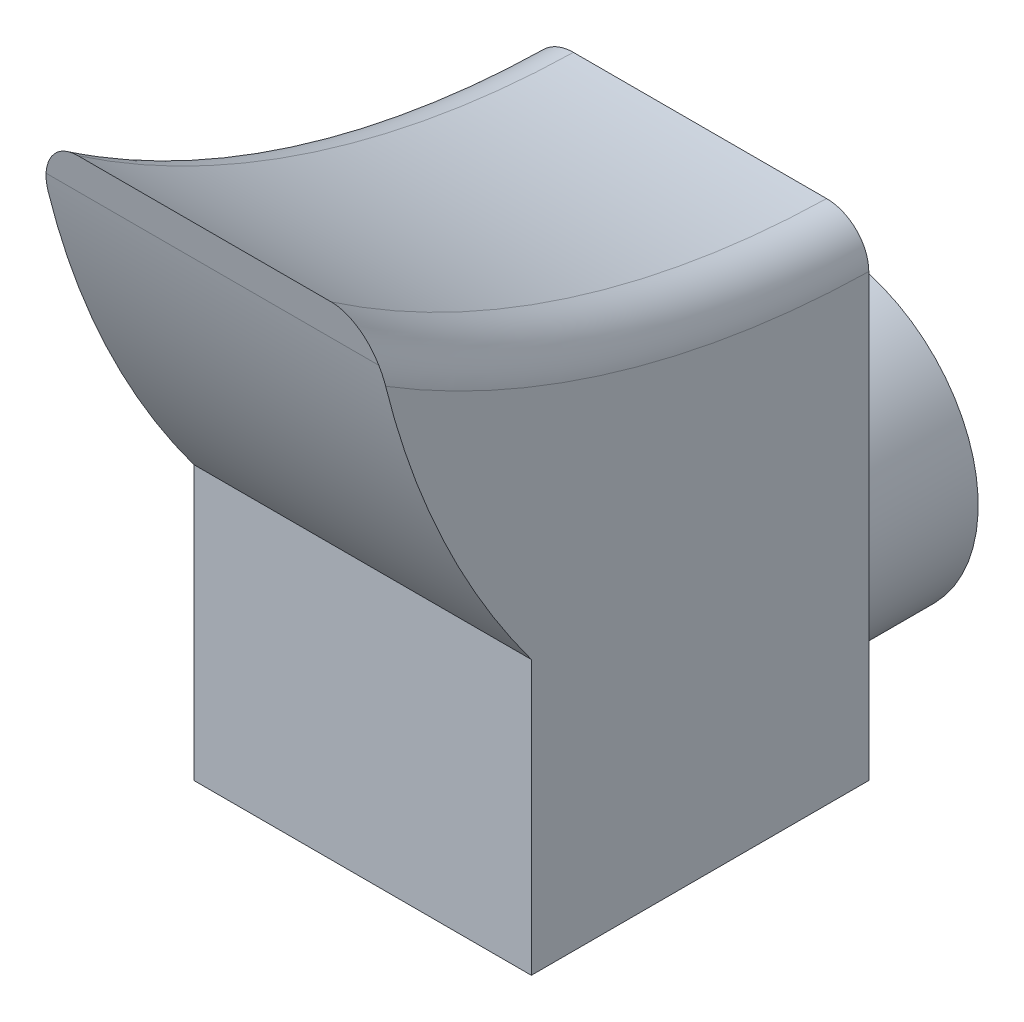
SolidWorks part; units mm, degrees
ref_plane "Front Plane" through (0, 0, 0) normal (0, 0, 1) x (1, 0, 0)
ref_plane "Top Plane" through (0, 0, 0) normal (0, 1, 0) x (1, 0, 0)
ref_plane "Right Plane" through (0, 0, 0) normal (1, 0, 0) x (0, 0, -1)
sketch "Sketch1" plane through (0, 0, 0) normal (0, 0, 1) x (1, 0, 0)
  line L6 (-39.1338, -35.8463) -> (-39.1338, -33.2005)
  line L7 (-42.1338, -35.8462) -> (-42.1338, -33.2005)
  line L10 (-40.6338, -38.5234) -> (-38.6289, -38.5234)
  line L11 (-40.6338, -38.5234) -> (-42.6335, -38.4759)
  line L13 (-42.4445, -30.5234) -> (-40.6338, -30.5234)
  line L14 (-38.6289, -38.5234) -> (-38.6289, -30.5234)
  line L15 (-38.6289, -30.5234) -> (-40.6338, -30.5234)
  line L16 (-42.6335, -38.4759) -> (-42.6335, -30.5234)
  line L17 (-42.6335, -30.5234) -> (-42.4445, -30.5234)
  arc A6 (-42.1338, -35.8462) -> (-39.1338, -35.8463) centre (-40.6338, -34.5234) ccw
  arc A7 (-39.1338, -33.2005) -> (-42.1338, -33.2005) centre (-40.6338, -34.5234) ccw
extrude "Boss-Extrude1" add sketch "Sketch1" against normal blind 5
sketch "Sketch2" plane through (-38.6289, 0, 0) normal (1, 0, 0) x (0, 0, -1)
  line L4 (0, -30.5234) -> (0, -38.5234)
  line L5 (0, -38.5234) -> (5, -38.5234)
  line L6 (5, -38.5234) -> (5, -30.5234)
  line L7 (5, -30.5234) -> (0, -30.5234)
  line L8 (0, -30.5234) -> (0, -38.5234)
  line L9 (0, -38.5234) -> (5, -38.5234)
  line L10 (5, -38.5234) -> (5, -30.5234)
  line L11 (5, -30.5234) -> (0, -30.5234)
  dimension "D1" = 0
extrude "Boss-Extrude2" add sketch "Sketch2" along normal blind 1
sketch "Sketch3" plane through (-42.6335, 0, 0) normal (-1, 0, 0) x (0, 0, 1)
  line L4 (0, -38.4759) -> (0, -30.5234)
  line L5 (0, -30.5234) -> (-5, -30.5234)
  line L6 (-5, -30.5234) -> (-5, -38.4759)
  line L7 (-5, -38.4759) -> (0, -38.4759)
  line L8 (0, -38.4759) -> (0, -30.5234)
  line L9 (0, -30.5234) -> (-5, -30.5234)
  line L10 (-5, -30.5234) -> (-5, -38.4759)
  line L11 (-5, -38.4759) -> (0, -38.4759)
  dimension "D1" = 0
extrude "Boss-Extrude3" add sketch "Sketch3" along normal blind 1
sketch "Sketch4" plane through (0, 0, 0) normal (0, 0, 1) x (1, 0, 0)
  circle A0 centre (-40.6338, -34.5232) radius 2.6168
  arc A2 (-38.6219, -36.1966) -> (-38.0838, -35.1107) centre (-40.6337, -34.5233) ccw
  arc A3 (-38.0838, -33.936) -> (-38.6219, -32.8502) centre (-40.6337, -34.5234) ccw
  arc A4 (-42.6457, -32.8502) -> (-43.1838, -33.936) centre (-40.6338, -34.5234) ccw
  arc A5 (-43.1838, -35.1107) -> (-42.6457, -36.1966) centre (-40.6338, -34.5233) ccw
  spline S6 degree 3 poles (-38.6836, -36.2325) (-38.6587, -36.2324) (-38.6377, -36.2156) (-38.6219, -36.1966) knots 0 0 0 0 0.000073 0.000073 0.000073 0.000073 weights 1 1 1 1
  spline S7 degree 3 poles (-38.6219, -32.8502) (-38.6376, -32.8312) (-38.6586, -32.8145) (-38.6834, -32.8142) knots 0 0 0 0 0.000073 0.000073 0.000073 0.000073 weights 1 1 1 1
  spline S12 degree 3 poles (-42.6457, -36.1966) (-42.6298, -36.2155) (-42.6086, -36.2322) (-42.5838, -36.2321) knots 0 0 0 0 0.000073 0.000073 0.000073 0.000073 weights 1 1 1 1
  spline S13 degree 3 poles (-42.5838, -32.8147) (-42.6086, -32.8146) (-42.6298, -32.8313) (-42.6457, -32.8502) knots 0 0 0 0 0.000073 0.000073 0.000073 0.000073 weights 1 1 1 1
  line M15 (-39.1338, -33.2005) -> (-39.1338, -35.8463)
  arc M16 (-39.1338, -35.8463) -> (-42.1338, -35.8462) centre (-40.6338, -34.5234) cw
  line M17 (-42.1338, -35.8462) -> (-42.1338, -33.2005)
  arc M18 (-42.1338, -33.2005) -> (-39.1338, -33.2005) centre (-40.6338, -34.5234) cw
extrude "Cut-Extrude1" cut sketch "Sketch4" against normal up to surface (7.05 mm away) contours A0 | M15 M18 M17 M16 region at (-38.1073, -34.8105, 0) region at (-40.6338, -34.5234, 0)
sketch "Sketch5" plane through (-43.6335, 0, 0) normal (-1, 0, 0) x (0, 0, 1)
  line L4 (-5, -38.4759) -> (0, -38.4759)
  line L5 (0, -38.4759) -> (0, -30.5234)
  line L6 (0, -30.5234) -> (-5, -30.5234)
  line L7 (-5, -30.5234) -> (-5, -38.4759)
  line L8 (-5, -38.4759) -> (0, -38.4759)
  line L9 (0, -38.4759) -> (0, -30.5234)
  line L10 (0, -30.5234) -> (-5, -30.5234)
  line L11 (-5, -30.5234) -> (-5, -38.4759)
  dimension "D1" = 0
extrude "Boss-Extrude4" add sketch "Sketch5" along normal blind 1
sketch "Sketch6" plane through (-37.6289, 0, 0) normal (1, 0, 0) x (0, 0, -1)
  line L4 (5, -30.5234) -> (0, -30.5234)
  line L5 (0, -30.5234) -> (0, -38.5234)
  line L6 (0, -38.5234) -> (5, -38.5234)
  line L7 (5, -38.5234) -> (5, -30.5234)
  line L8 (5, -30.5234) -> (0, -30.5234)
  line L9 (0, -30.5234) -> (0, -38.5234)
  line L10 (0, -38.5234) -> (5, -38.5234)
  line L11 (5, -38.5234) -> (5, -30.5234)
  dimension "D1" = 0
extrude "Boss-Extrude5" add sketch "Sketch6" along normal blind 1
sketch "Sketch7" plane through (0, 0, -5) normal (0, 0, -1) x (-1, 0, 0)
  line L0 (36.6289, -30.5234) -> (36.6289, -38.5234)
  line L1 (36.6289, -30.5234) -> (44.6335, -30.5234) construction
  line L2 (38.017, -34.5232) -> (38.017, -38.5234)
  line L3 (40.6338, -38.5234) -> (36.6289, -38.5234) construction
  line L4 (38.017, -38.5234) -> (36.6289, -38.5234)
  line L5 (38.017, -34.5232) -> (38.017, -30.5234)
  line L6 (38.017, -30.5234) -> (36.6289, -30.5234)
  line L7 (43.2506, -34.5232) -> (43.2506, -30.5234)
  line L8 (43.2506, -30.5234) -> (44.6335, -30.5234)
  line L9 (44.6335, -30.5234) -> (44.6335, -38.4759) construction
  line L10 (44.6335, -30.5234) -> (44.6335, -38.4759)
  line L11 (44.6335, -38.4759) -> (43.2506, -38.4759)
  line L12 (44.6335, -38.4759) -> (42.6335, -38.4759) construction
  line L13 (43.2506, -38.4759) -> (43.2506, -34.5232)
  circle A0 centre (40.6338, -34.5232) radius 2.6168 construction
extrude "Boss-Extrude6" add sketch "Sketch7" along normal blind 1
sketch "Sketch8" plane through (0, -30.5234, 0) normal (0, 1, 0) x (1, 0, 0)
  line L0 (-44.6335, 0) -> (-44.6335, 6) construction
  line L1 (-44.6335, 0) -> (-36.6289, 0)
  line L2 (-44.6335, 0) -> (-44.6335, 6)
  line L3 (-44.6335, 6) -> (-36.6289, 6)
  line L4 (-36.6289, 0) -> (-36.6289, 6)
  line L5 (-38.017, 6) -> (-36.6289, 6) construction
extrude "Boss-Extrude7" add sketch "Sketch8" along normal blind 3.5
sketch "Sketch9" plane through (0, 0, 0) normal (0, 0, 1) x (1, 0, 0)
  line L0 (-40.6338, -38.5234) -> (-36.6289, -38.5234) construction
  line L1 (-36.6289, -38.5234) -> (-44.6335, -38.5234)
  line L2 (-36.6289, -38.5234) -> (-36.6289, -27.0234)
  line L3 (-36.6289, -27.0234) -> (-44.6335, -27.0234)
  line L4 (-44.6335, -38.5234) -> (-44.6335, -27.0234)
  line L5 (-44.6335, -27.0234) -> (-36.6289, -27.0234) construction
  line L6 (-44.6335, -38.4759) -> (-44.6335, -27.0234) construction
extrude "Boss-Extrude8" add sketch "Sketch9" along normal blind 5
sketch "Sketch10" plane through (-44.6335, 0, 0) normal (-1, 0, 0) x (0, 0, 1)
  line L0 (-6, -27.0234) -> (5, -27.0234) construction
  line L5 (5, -27.0234) -> (-5.2433, -27.0234)
  line L6 (-5.2433, -27.0234) -> (5.6988, -19.6464)
  line L7 (5, -38.5234) -> (7.9533, -27.0234)
  line L8 (5, -27.0234) -> (5, -38.5234) construction
  line L9 (5, -38.5234) -> (5, -27.0234)
  arc A0 (7.9533, -27.0234) -> (5.6988, -19.6464) centre (-5.2433, -27.0234) ccw
extrude "Boss-Extrude9" add sketch "Sketch10" against normal up to surface (8.0045 mm away) up to face at (-36.6289, -32.7734, -0.5)
sketch "Sketch13" plane through (0, 0, -6) normal (0, 0, -1) x (-1, 0, 0)
  line L0 (36.6289, -27.0234) -> (44.6335, -27.0234) construction
  line L1 (36.6289, -27.0234) -> (44.6335, -27.0234)
  line L2 (36.6289, -27.0234) -> (36.6289, -19.6464)
  line L3 (36.6289, -19.6464) -> (44.6335, -19.6464)
  line L4 (44.6335, -27.0234) -> (44.6335, -19.6464)
  line L5 (36.6289, -19.6464) -> (44.6335, -19.6464) construction
extrude "Cut-Extrude2" cut sketch "Sketch13" against normal blind 25
sketch "Sketch14" plane through (-36.6289, 0, 0) normal (1, 0, 0) x (0, 0, -1)
  line L0 (-5, -38.5234) -> (-5, -27.0234)
  line L1 (-7.9533, -27.0234) -> (6, -27.0234) construction
  line L2 (-5, -27.0234) -> (-7.9533, -27.0234)
  line L3 (-7.9533, -27.0234) -> (-5, -38.5234)
extrude "Cut-Extrude3" cut sketch "Sketch14" against normal blind 25
sketch "Sketch15" plane through (-44.6335, 0, 0) normal (-1, 0, 0) x (0, 0, 1)
  line L0 (-6, -27.0234) -> (5, -27.0234) construction
  line L1 (5.7484, -23.2718) -> (5, -27.0234)
  line L2 (5, -27.0234) -> (5, -38.5234) construction
  line L3 (5, -27.0234) -> (-6, -27.0234)
  arc A0 (5.7484, -23.2718) -> (-6, -27.0234) centre (-6.4702, -5.2796) cw
extrude "Boss-Extrude10" add sketch "Sketch15" against normal up to surface (8.0045 mm away) up to face at (-36.6289, -32.7734, -0.5)
sketch "Sketch16" plane through (-44.6335, 0, 0) normal (-1, 0, 0) x (0, 0, 1)
  line L0 (5.7484, -23.2718) -> (5, -27.0234)
  line L1 (5, -27.0234) -> (5.7484, -23.2718) construction
  line L2 (5, -27.0234) -> (2.706, -38.5234)
  line L3 (5, -38.5234) -> (0, -38.5234) construction
  line L4 (2.706, -38.5234) -> (6.3668, -38.5234)
  line L5 (6.3668, -38.5234) -> (5.7484, -23.2718)
extrude "Cut-Extrude4" cut sketch "Sketch16" against normal blind 25
sketch "Sketch17" plane through (-44.6335, 0, 0) normal (-1, 0, 0) x (0, 0, 1)
  line L0 (-6, -38.4759) -> (0, -38.4759) construction
  line L1 (-6, -38.4759) -> (2.706, -38.5234)
  line L2 (2.706, -38.5234) -> (0, -38.5234) construction
  line L3 (2.706, -38.5234) -> (5.7484, -23.2718)
  arc A0 (5.7484, -23.2718) -> (-6, -38.4759) centre (-14.596, -19.6925) cw
  arc A1 (-6, -27.0234) -> (5.7484, -23.2718) centre (-6.4702, -5.2796) ccw construction
  line M5 (2.706, -38.5234) -> (5.7484, -23.2718)
  line M8 (-6, -38.4759) -> (0, -38.4759)
  line M9 (0, -38.4759) -> (0, -38.5234)
extrude "Cut-Extrude5" cut sketch "Sketch17" against normal blind 25 contours A0 L1 M5 M8 M9 region at (-44.6335, -35.1046, 0.9901)
sketch "Sketch18" plane through (0, -38.4759, 0) normal (0, 1, 0) x (1, 0, 0)
  line L0 (-36.6289, -2.706) -> (-36.6289, 0) construction
  line L2 (-41.2553, 0) -> (-44.6335, 0) construction
  line L3 (-44.6335, 0) -> (-44.6335, -2.706) construction
  line L4 (-36.6289, -2.706) -> (-44.6335, -2.706) construction
  line L5 (-36.6289, -2.706) -> (-36.6289, 0)
  line L6 (-42.6335, 5) -> (-42.6335, 0)
  line L7 (-42.6335, 0) -> (-36.6289, 0)
  line L8 (-36.6289, 0) -> (-36.6289, 6)
  line L9 (-36.6289, 6) -> (-38.017, 6)
  line L10 (-38.017, 6) -> (-38.017, 5)
  line L11 (-38.017, 5) -> (-42.6335, 5)
  line L12 (-42.6335, 5) -> (-42.6335, 0)
  line L14 (-36.6289, 0) -> (-36.6289, 6)
  line L15 (-36.6289, 6) -> (-38.017, 6)
  line L16 (-38.017, 6) -> (-38.017, 5)
  line L17 (-38.017, 5) -> (-42.6335, 5)
  line L19 (-42.6335, 0) -> (-44.6335, 0)
  line L20 (-44.6335, 0) -> (-44.6335, -2.706)
  line L21 (-36.6289, -2.706) -> (-44.6335, -2.706)
  dimension "D1" = 0
extrude "Cut-Extrude6" cut sketch "Sketch18" against normal blind 2
sketch "Sketch19" plane through (-44.6335, 0, 0) normal (-1, 0, 0) x (0, 0, 1)
  line L0 (-6, -38.4759) -> (2.0022, -38.4759)
  line L2 (2.0022, -38.4759) -> (2.0022, -31.9891)
  line L3 (0, -34.3097) -> (0, -36.7103)
  line L4 (0, -36.7103) -> (-2.887, -36.7103)
  arc A0 (-6, -38.4759) -> (5.5646, -24.1931) centre (-14.596, -19.6925) ccw construction
  arc A1 (2.0022, -31.9891) -> (5.5646, -24.1931) centre (-14.596, -19.6925) ccw
  arc A2 (-6, -38.4759) -> (-2.887, -36.7103) centre (-14.596, -19.6925) ccw
  arc A3 (0, -34.3097) -> (5.5646, -24.1931) centre (-14.596, -19.6925) ccw
  arc M2 (-6, -38.4759) -> (5.5646, -24.1931) centre (-14.596, -19.6925) ccw
extrude "Boss-Extrude11" add sketch "Sketch19" against normal up to surface (8.0045 mm away) contours L3 L4 L0 L2 M2 region at (-44.6335, -37.7502, -4.3544) up to face at (-36.6289, -28.7928, 0.3151)
sketch "Sketch21" plane through (0, 0, -6) normal (0, 0, -1) x (-1, 0, 0)
  line L8 (36.6289, -38.4759) -> (38.017, -38.4759)
  line L9 (38.017, -38.4759) -> (38.017, -30.5234)
  line L10 (38.017, -30.5234) -> (43.2506, -30.5234)
  line L11 (43.2506, -30.5234) -> (43.2506, -38.4759)
  line L12 (43.2506, -38.4759) -> (44.6335, -38.4759)
  line L13 (44.6335, -38.4759) -> (44.6335, -27.0234)
  line L14 (44.6335, -27.0234) -> (36.6289, -27.0234)
  line L15 (36.6289, -27.0234) -> (36.6289, -38.4759)
  line L16 (36.6289, -38.4759) -> (38.017, -38.4759)
  line L17 (38.017, -38.4759) -> (38.017, -30.5234)
  line L18 (38.017, -30.5234) -> (43.2506, -30.5234)
  line L19 (43.2506, -30.5234) -> (43.2506, -38.4759)
  line L20 (43.2506, -38.4759) -> (44.6335, -38.4759)
  line L21 (44.6335, -38.4759) -> (44.6335, -27.0234)
  line L22 (44.6335, -27.0234) -> (36.6289, -27.0234)
  line L23 (36.6289, -27.0234) -> (36.6289, -38.4759)
  dimension "D1" = 0
extrude "Boss-Extrude12" add sketch "Sketch21" against normal up to surface (8.0022 mm away) up to face at (-40.6312, -35.2325, 2.0022)
sketch "Sketch22" plane through (0, 0, -5) normal (0, 0, -1) x (-1, 0, 0)
  line L3 (38.017, -37.9852) -> (43.2506, -37.9852)
  line L4 (43.2506, -37.9852) -> (43.2506, -34.5232)
  line L5 (38.017, -34.5232) -> (38.017, -37.9852)
  arc A0 (43.2506, -34.5232) -> (38.017, -34.5232) centre (40.6338, -34.5232) ccw construction
  arc A1 (38.017, -34.5232) -> (43.2506, -34.5232) centre (40.6338, -34.5232) ccw
  arc A2 (38.017, -34.5232) -> (43.2506, -34.5232) centre (40.6338, -34.5232) ccw
  arc A3 (43.2506, -34.5232) -> (38.017, -34.5232) centre (40.6338, -34.5232) ccw
  dimension "D1" = 0
extrude "Cut-Extrude7" cut sketch "Sketch22" against normal up to surface (5 mm away) up to face at (-40.6338, -34.7093, 0)
sketch "Sketch23" plane through (0, 0, -5) normal (0, 0, -1) x (-1, 0, 0)
  line L3 (38.017, -37.9852) -> (43.2506, -37.9852)
  line L4 (43.2506, -37.9852) -> (43.2506, -34.5232)
  line L5 (38.017, -34.5232) -> (38.017, -37.9852)
  line L6 (38.017, -37.9852) -> (43.2506, -37.9852)
  line L7 (43.2506, -37.9852) -> (43.2506, -34.5232)
  line L8 (38.017, -34.5232) -> (38.017, -37.9852)
  line L9 (43.2506, -34.5232) -> (43.2506, -30.5234)
  line L10 (43.2506, -30.5234) -> (38.017, -30.5234)
  line L11 (38.017, -30.5234) -> (38.017, -34.5232)
  line L12 (43.2506, -34.5232) -> (43.2506, -30.5234)
  line L13 (43.2506, -30.5234) -> (38.017, -30.5234)
  line L14 (38.017, -30.5234) -> (38.017, -34.5232)
  arc A1 (38.017, -34.5232) -> (43.2506, -34.5232) centre (40.6338, -34.5232) ccw
  arc A2 (38.017, -34.5232) -> (43.2506, -34.5232) centre (40.6338, -34.5232) ccw
  arc A3 (43.2506, -34.5232) -> (38.017, -34.5232) centre (40.6338, -34.5232) ccw
  arc A4 (43.2506, -34.5232) -> (38.017, -34.5232) centre (40.6338, -34.5232) ccw
  arc M9 (38.017, -34.5232) -> (43.2506, -34.5232) centre (40.6338, -34.5232) cw
  line M10 (43.2506, -34.5232) -> (43.2506, -30.5234)
  line M11 (43.2506, -30.5234) -> (38.017, -30.5234)
  line M12 (38.017, -30.5234) -> (38.017, -34.5232)
  dimension "D1" = 0
  dimension "D2" = 0
extrude "Boss-Extrude13" add sketch "Sketch23" against normal up to surface (5 mm away) contours A2 L8 L6 L7 | M12 M9 M10 M11 region at (-40.6338, -37.1606, -5) region at (-40.6338, -31.5834, -5) up to face at (-40.6338, -35.2633, 0)
sketch "Sketch24" plane through (0, 0, -5) normal (0, 0, -1) x (-1, 0, 0)
  line L0 (43.2506, -34.5232) -> (43.2506, -30.5234) construction
  line L1 (43.2506, -30.5234) -> (38.017, -30.5234) construction
  line L2 (38.017, -30.5234) -> (38.017, -34.5232) construction
  line L3 (38.017, -37.9852) -> (43.2506, -37.9852) construction
  line L4 (43.2506, -37.9852) -> (43.2506, -34.5232) construction
  line L5 (38.017, -34.5232) -> (38.017, -37.9852) construction
  line L6 (43.2506, -34.5232) -> (43.2506, -30.5234)
  line L7 (43.2506, -30.5234) -> (38.017, -30.5234)
  line L8 (38.017, -30.5234) -> (38.017, -34.5232)
  line L9 (38.017, -37.9852) -> (43.2506, -37.9852)
  line L10 (43.2506, -37.9852) -> (43.2506, -34.5232)
  line L11 (38.017, -34.5232) -> (38.017, -37.9852)
  circle A7 centre (40.6338, -34.5232) radius 1.6
extrude "Boss-Extrude14" add sketch "Sketch24" against normal up to surface (5 mm away) up to face at (-38.017, -34.5232, 0)
sketch "Sketch25" plane through (0, 0, -5) normal (0, 0, -1) x (-1, 0, 0)
  line L4 (38.017, -37.9852) -> (43.2506, -37.9852)
  line L5 (43.2506, -37.9852) -> (43.2506, -30.5234)
  line L6 (43.2506, -30.5234) -> (38.017, -30.5234)
  line L7 (38.017, -30.5234) -> (38.017, -37.9852)
  line L8 (38.017, -37.9852) -> (43.2506, -37.9852)
  line L9 (43.2506, -37.9852) -> (43.2506, -30.5234)
  line L10 (43.2506, -30.5234) -> (38.017, -30.5234)
  line L11 (38.017, -30.5234) -> (38.017, -37.9852)
  circle A0 centre (40.6338, -34.5232) radius 1.6 construction
  circle A1 centre (40.6338, -34.5232) radius 1.6
  dimension "D1" = 0
extrude "Boss-Extrude15" add sketch "Sketch25" along normal up to surface (1 mm away) up to face at (-40.6325, -33.6246, -6)
sketch "Sketch26" plane through (0, -38.4759, 0) normal (0, -1, 0) x (1, 0, 0)
  line L0 (-36.6289, -6) -> (-36.6289, 2.0022) construction
  line L1 (-44.6335, -6) -> (-36.6289, -6)
  line L2 (-44.6335, -6) -> (-44.6335, -4.4983)
  line L3 (-44.6335, -4.4983) -> (-36.6289, -4.4983)
  line L4 (-36.6289, -6) -> (-36.6289, -4.4983)
extrude "Boss-Extrude16" add sketch "Sketch26" against normal blind 2
sketch "Sketch27" plane through (0, 0, -6) normal (0, 0, -1) x (-1, 0, 0)
  circle A0 centre (40.6338, -34.5232) radius 1.6 construction
  circle A1 centre (40.6338, -34.5232) radius 1.6
  circle A2 centre (40.6338, -34.5232) radius 3.6
extrude "Boss-Extrude17" add sketch "Sketch27" along normal blind 3
sketch "Sketch28" plane through (0, 0, -9) normal (0, 0, -1) x (-1, 0, 0)
  circle A0 centre (40.6338, -34.5232) radius 2.25
extrude "Cut-Extrude8" cut sketch "Sketch28" against normal up to surface (9 mm away) up to face at (-39.0338, -34.5232, 0)
fillet "Fillet1" radius 1 1 edges at (-44.6335, -25.9978, 0.1457) type face fillet first side face at (-40.6312, -25.5727, 0.0099) second side face at (-44.6335, -30.7443, 0.6663)
fillet "Fillet2" radius 1 1 edges at (-36.6289, -25.9978, 0.1457) type face fillet first side face at (-40.1312, -25.5727, 0.0099) second side face at (-36.6289, -30.7443, 0.6663)
